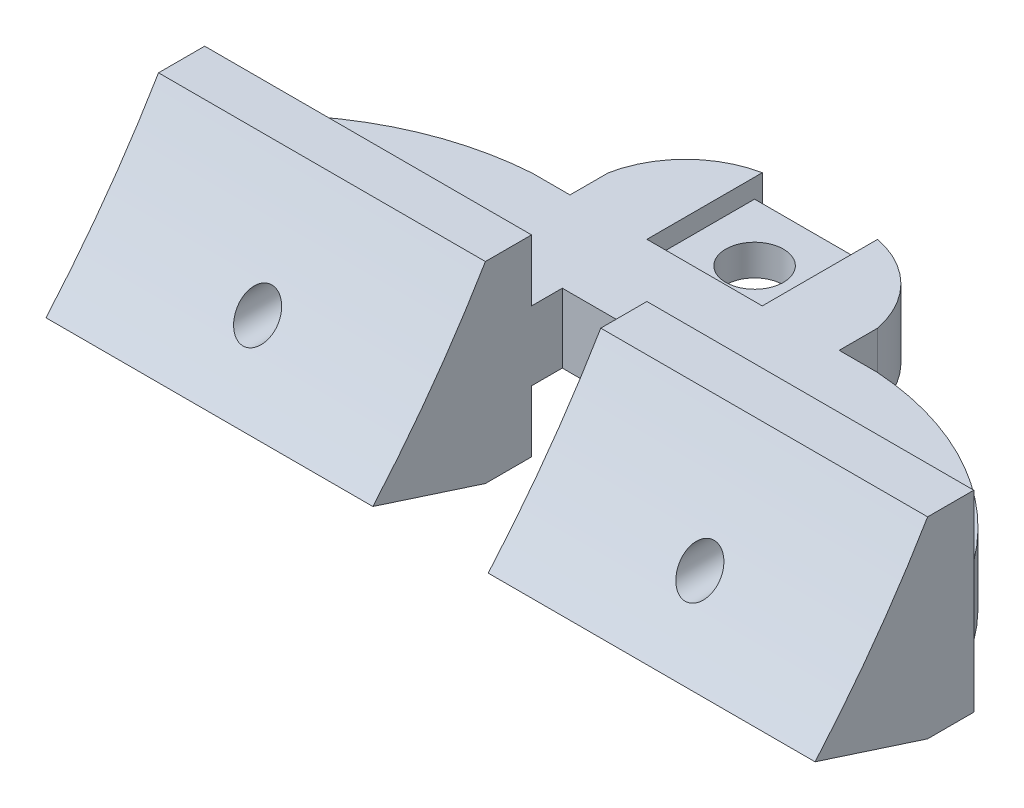
SolidWorks part; units mm, degrees
material "PMMA"
ref_plane "Plan de face" through (0, 0, 0) normal (0, 0, 1) x (1, 0, 0)
ref_plane "Plan de dessus" through (0, 0, 0) normal (0, 1, 0) x (1, 0, 0)
ref_plane "Plan de droite" through (0, 0, 0) normal (1, 0, 0) x (0, 0, -1)
sketch "Esquisse1" plane through (0, 0, 0) normal (0, 0, 1) x (1, 0, 0)
  line L1 (0, 0) -> (6, 0)
  line L2 (0, 0) -> (0, 1.61)
  line L3 (0, 1.61) -> (6, 1.61)
  line L4 (6, 0) -> (6, 1.61)
  dimension "D1" = 6
  dimension "D2" = 1.61
extrude "Boss.-Extru.1" add sketch "Esquisse1" against normal blind 6
sketch "Esquisse2" plane through (0, 0, 0) normal (0, 1, 0) x (1, 0, 0)
  line L0 (0, 6) -> (0, 0) construction
  line L1 (6, 0) -> (0, 0) construction
  circle A0 centre (3, 3) radius 1.5
  dimension "D3" = 3
  dimension "D1" = 3
  dimension "D2" = 3
extrude "Enlèv. mat.-Extru.3" cut sketch "Esquisse2" along normal through all contours A0
sketch "Esquisse5" plane through (0, 0, 0) normal (0, 0, 1) x (1, 0, 0)
  line L0 (0, 0) -> (6, 0) construction
  line L1 (3, 0.8) -> (-17, 0.8)
  line L2 (3, 0.8) -> (3, 5.8)
  line L3 (3, 5.8) -> (-17, 5.8)
  line L4 (-17, 0.8) -> (-17, 5.8)
  line L5 (3, 0.8) -> (-17, 0.8)
  line L6 (3, 0.8) -> (3, -4.2)
  line L7 (3, -4.2) -> (-17, -4.2)
  line L8 (-17, 0.8) -> (-17, -4.2)
  line L9 (3, 0.8) -> (23, 0.8)
  line L10 (3, 0.8) -> (3, 5.8)
  line L11 (3, 5.8) -> (23, 5.8)
  line L12 (23, 0.8) -> (23, 5.8)
  line L13 (3, 0.8) -> (23, 0.8)
  line L14 (3, 0.8) -> (3, -4.2)
  line L15 (3, -4.2) -> (23, -4.2)
  line L16 (23, 0.8) -> (23, -4.2)
  dimension "D1" = 0.8
  dimension "D2" = 5
  dimension "D3" = 5
  dimension "D4" = 20
  dimension "D5" = 20
extrude "Boss.-Extru.2" add sketch "Esquisse5" along normal blind 8 separate body contours L2 L1 L4 L3 | L10 L9 L12 L11 | L14 L13 L16 L15 | L6 L5 L8 L7
sketch "Esquisse6" plane through (0, 0, 0) normal (0, 0, -1) x (-1, 0, 0)
  line L1 (-23, 5.8) -> (17, 5.8)
  line L2 (-23, 5.8) -> (-23, -4.2)
  line L3 (-23, -4.2) -> (17, -4.2)
  line L4 (17, 5.8) -> (17, -4.2)
extrude "Boss.-Extru.3" add sketch "Esquisse6" along normal blind 0.4
sketch "Esquisse7" plane through (0, 0, -0.4) normal (0, 0, -1) x (-1, 0, 0)
  line L1 (0, 1.61) -> (4, 1.61)
  line L2 (0, 1.61) -> (0, 0.01)
  line L3 (0, 0.01) -> (4, 0.01)
  line L4 (4, 1.61) -> (4, 0.01)
  line L5 (0, 1.61) -> (4, 1.61)
  line L6 (0, 1.61) -> (0, 2.61)
  line L7 (0, 2.61) -> (4, 2.61)
  line L8 (4, 1.61) -> (4, 2.61)
  line L9 (0, 0.01) -> (4, 0.01)
  line L10 (0, 0.01) -> (0, -0.99)
  line L11 (0, -0.99) -> (4, -0.99)
  line L12 (4, 0.01) -> (4, -0.99)
  line L13 (-6, 0) -> (-10, 0)
  line L14 (-6, 0) -> (-6, 1.6)
  line L15 (-6, 1.6) -> (-10, 1.6)
  line L16 (-10, 0) -> (-10, 1.6)
  line L17 (-10, 1.6) -> (-6, 1.6)
  line L18 (-10, 1.6) -> (-10, 2.6)
  line L19 (-10, 2.6) -> (-6, 2.6)
  line L20 (-6, 1.6) -> (-6, 2.6)
  line L21 (-10, 0) -> (-6, 0)
  line L22 (-10, 0) -> (-10, -1)
  line L23 (-10, -1) -> (-6, -1)
  line L24 (-6, 0) -> (-6, -1)
  line M16 (0, 1.61) -> (0, 0)
  line M18 (-6, 0) -> (-6, 1.61)
  dimension "D1" = 4
  dimension "D2" = 4
  dimension "D3" = 1
  dimension "D4" = 1
  dimension "D5" = 1
  dimension "D6" = 1
  dimension "D7" = 1.6
extrude "Boss.-Extru.4" add sketch "Esquisse7" along normal blind 6 contours L24 L13 L22 L23 | L15 L20 L19 L18 | L16 L13 L15 M18 | L1 L8 L7 L6 | L4 L1 L3 M16 | L12 L3 L10 L11 region at (-2, 2.11, -0.4) region at (-2, 0.81, -0.4) region at (-2, -0.49, -0.4) region at (8, -0.5, -0.4) region at (8, 0.8, -0.4) region at (8, 2.1, -0.4)
sketch "Esquisse8" plane through (0, -1, 0) normal (0, -1, 0) x (1, 0, 0)
  line L1 (10, -0.4) -> (6, -0.4)
  line L2 (10, -0.4) -> (10, -6.4)
  line L3 (10, -6.4) -> (6, -6.4)
  line L4 (6, -0.4) -> (6, -6.4)
  line L5 (0, -6.4) -> (-4, -6.4)
  line L6 (0, -6.4) -> (0, -0.4)
  line L7 (0, -0.4) -> (-4, -0.4)
  line L8 (-4, -6.4) -> (-4, -0.4)
  arc A0 (0, -6.4) -> (-4, -0.4) centre (1, -1.4) cw
  arc A1 (6, -6.4) -> (10, -0.4) centre (5, -1.4) ccw
  line M3 (6, -6.4) -> (10, -6.4)
  line M4 (10, -6.4) -> (10, -0.4)
extrude "Enlèv. mat.-Extru.4" cut sketch "Esquisse8" against normal blind 6 contours A1 M3 M4 | L5 A0 L8 region at (8.9616, -1, -5.3616) region at (-2.9616, -1, -5.3616)
sketch "Esquisse9" plane through (0, 0, 8) normal (0, 0, 1) x (1, 0, 0)
  line L0 (-17, -4.2) -> (23, -4.2) construction
  line L1 (-17, 5.8) -> (0, 5.8)
  line L2 (-17, 5.8) -> (-17, -4.2)
  line L3 (-17, -4.2) -> (0, -4.2)
  line L4 (0, 5.8) -> (0, -4.2)
  line L6 (0, 5.8) -> (6, 5.8)
  line L7 (0, 5.8) -> (0, -4.2)
  line L8 (0, -4.2) -> (6, -4.2)
  line L9 (6, 5.8) -> (6, -4.2)
  line M4 (-17, -4.2) -> (23, -4.2)
  line M6 (23, 5.8) -> (-17, 5.8)
  dimension "D1" = 17
  dimension "6" = 6
extrude "Enlèv. mat.-Extru.5" cut sketch "Esquisse9" against normal blind 4 contours L9 L4 M6 M4 region at (3, 0.8, 8)
sketch "Esquisse10" plane through (0, -4.2, 0) normal (0, -1, 0) x (1, 0, 0)
  line L0 (-17, -0.4) -> (-17, 8) construction
  line L1 (-17, 5.6) -> (0, 5.6)
  line L2 (-17, 5.6) -> (-17, -0.4)
  line L3 (-17, -0.4) -> (0, -0.4)
  line L4 (0, 5.6) -> (0, -0.4)
  line L5 (23, -0.4) -> (-17, -0.4) construction
  line L6 (0, -0.4) -> (6, -0.4) construction
  line L7 (23, -0.4) -> (23, 8) construction
  line L8 (6, -0.4) -> (23, -0.4)
  line L9 (6, -0.4) -> (6, 5.6)
  line L10 (6, 5.6) -> (23, 5.6)
  line L11 (23, -0.4) -> (23, 5.6)
  line L13 (0, -0.4) -> (6, -0.4)
  line L14 (0, -0.4) -> (0, 4)
  line L15 (0, 4) -> (6, 4)
  line L16 (6, -0.4) -> (6, 4)
  line M5 (6, 8) -> (6, 4)
  line M6 (6, 4) -> (0, 4)
  line M7 (0, 4) -> (0, 8)
  line M9 (-17, 8) -> (-17, -0.4)
  line M10 (-17, -0.4) -> (23, -0.4)
  line M11 (23, -0.4) -> (23, 8)
  dimension "D1" = 6
  dimension "D2" = 6
extrude "Enlèv. mat.-Extru.6" cut sketch "Esquisse10" against normal blind 3.2 contours L4 L1 M7 M9 M10 | L9 L4 M10 M6 | L10 L9 M5 M10 M11 region at (-8.5, -4.2, 2.6) region at (3, -4.2, 1.8) region at (14.5, -4.2, 2.6)
sketch "Esquisse11" plane through (0, 5.8, 0) normal (0, 1, 0) x (1, 0, 0)
  line L0 (0, -4) -> (0, -8) construction
  line L1 (-17, 0.4) -> (0, 0.4)
  line L2 (-17, 0.4) -> (-17, -5.6)
  line L3 (-17, -5.6) -> (0, -5.6)
  line L4 (0, 0.4) -> (0, -5.6)
  line L5 (23, 0.4) -> (23, -8) construction
  line L6 (6, 0.4) -> (23, 0.4)
  line L7 (6, 0.4) -> (6, -5.6)
  line L8 (6, -5.6) -> (23, -5.6)
  line L9 (23, 0.4) -> (23, -5.6)
  line L11 (0, 0.4) -> (6, 0.4)
  line L12 (0, 0.4) -> (0, -4)
  line L13 (0, -4) -> (6, -4)
  line L14 (6, 0.4) -> (6, -4)
  line M7 (6, -4) -> (6, -8)
  line M9 (23, -8) -> (23, 0.4)
  line M10 (23, 0.4) -> (-17, 0.4)
  line M11 (-17, 0.4) -> (-17, -8)
  line M13 (0, -8) -> (0, -4)
  line M14 (0, -4) -> (6, -4)
  dimension "D1" = 6
  dimension "D2" = 6
extrude "Enlèv. mat.-Extru.7" cut sketch "Esquisse11" against normal blind 3.2 contours L4 L3 M10 M11 M13 | L7 L4 M10 M14 | L8 L7 M7 M9 M10 region at (-8.5, 5.8, 2.6) region at (3, 5.8, 1.8) region at (14.5, 5.8, 2.6)
sketch "Esquisse12" plane through (0, -0.99, 0) normal (0, -1, 0) x (1, 0, 0)
  line L0 (0, -6.4) -> (0, -2.4)
  line L1 (0, -0.4) -> (-4, -0.4)
  line L2 (0, -0.4) -> (0, -2.4)
  line L3 (0, -2.4) -> (-4, -2.4)
  line L4 (-4, -0.4) -> (-4, -2.4)
  arc A0 (0, -6.4) -> (-4, -0.4) centre (1, -1.4) cw
  line M1 (-4, -0.4) -> (-4, -2.4)
  arc M2 (-4, -2.4) -> (0, -6.4) centre (1, -1.4) ccw
  line M3 (0, -6.4) -> (0, -0.4)
  line M4 (0, -0.4) -> (-4, -0.4)
extrude "Boss.-Extru.5" add sketch "Esquisse12" along normal blind 0.01 and the other way blind 3.61 contours L3 M3 M2 | L3 M3 M4 M1 region at (-1.5986, -0.99, -3.9986) region at (-2, -0.99, -1.4)
sketch "Esquisse13" plane through (0, 0, -0.4) normal (0, 0, 1) x (1, 0, 0)
  line L0 (0, 2.62) -> (-4, 2.62) construction
  line L1 (0, 2.6) -> (-3.9968, 2.6)
  line L2 (0, 2.6) -> (0, 2.62)
  line L3 (0, 2.62) -> (-3.9968, 2.62)
  line L4 (-3.9968, 2.6) -> (-3.9968, 2.62)
  line L6 (-3.9968, 2.6) -> (-4, 2.6)
  line L7 (-3.9968, 2.6) -> (-3.9968, 2.62)
  line L8 (-3.9968, 2.62) -> (-4, 2.62)
  line L9 (-4, 2.6) -> (-4, 2.62)
  line M1 (0, 2.6) -> (0, 2.62)
  line M2 (0, 2.62) -> (-4, 2.62)
  line M3 (-4, 2.62) -> (-4, 2.6)
  line M4 (-4, 2.6) -> (0, 2.6)
extrude "Enlèv. mat.-Extru.8" cut sketch "Esquisse13" against normal through all contours L4 M4 M1 M2 | L4 M4 M2 M3 region at (-1.9984, 2.61, -0.4) region at (-3.9984, 2.61, -0.4)
sketch "Esquisse14" plane through (0, -1, 0) normal (0, -1, 0) x (1, 0, 0)
  line L1 (-17, 5.6) -> (-4, 5.6)
  line L2 (-17, 5.6) -> (-17, -0.4)
  line L3 (-17, -0.4) -> (-4, -0.4)
  line L4 (-4, 5.6) -> (-4, -0.4)
  line L5 (10, -0.4) -> (23, -0.4)
  line L6 (10, -0.4) -> (10, 5.6)
  line L7 (10, 5.6) -> (23, 5.6)
  line L8 (23, -0.4) -> (23, 5.6)
  arc A0 (-17, 5.6) -> (-4, -0.4) centre (-4.9762, 14.5682) ccw
  arc A1 (10, -0.4) -> (23, 5.6) centre (10.9762, 14.5682) ccw
  line M4 (23, -0.4) -> (23, 5.6)
  line M10 (-17, 5.6) -> (-17, -0.4)
  line M11 (-17, -0.4) -> (-4, -0.4)
extrude "Enlèv. mat.-Extru.9" cut sketch "Esquisse14" against normal through all contours A0 M10 M11 | A1 L5 M4 region at (-14.1757, -1, 1.3209) region at (20.1757, -1, 1.3209)
sketch "Esquisse15" plane through (23, 0, 0) normal (1, 0, 0) x (0, 0, -1)
  line L0 (-13.8523, -2.3087) -> (-8, -4.2)
  line L7 (-5.6, -1) -> (-5.6, 2.6)
  line L8 (-5.6, 2.6) -> (-5.6, 5.8)
  line L9 (-5.6, 5.8) -> (-8, 5.8)
  line L10 (-8, 5.8) -> (-8, -4.2)
  line L11 (-8, -4.2) -> (-5.6, -4.2)
  line L12 (-5.6, -4.2) -> (-5.6, -1)
  line L16 (-8, 5.8) -> (-8, -4.2)
  arc A0 (-8, 5.8) -> (-13.8523, -2.3087) centre (-55.3392, 33.8) cw
  dimension "D1" = 28
  dimension "D4" = 0
  dimension "D3" = 10
  dimension "D2" = 55
extrude "Boss.-Extru.6" add sketch "Esquisse15" against normal blind 17
pattern_linear "Répétition linéaire1" count 2 spacing 23 along (-1, 0, 0) of "Boss.-Extru.6"
sketch "Esquisse17" plane through (0, 0, 5.6) normal (0, 0, -1) x (-1, 0, 0)
  line L0 (-6, -4.2) -> (-23, -4.2) construction
  line L1 (17, -4.2) -> (0, -4.2) construction
  line L2 (-23, 2.6) -> (-23, -1) construction
  line L3 (17, 2.6) -> (17, -1) construction
  circle A0 centre (8.5, 0.8) radius 1
  circle A1 centre (-14.5, 0.8) radius 1
  dimension "D1" = 2
  dimension "D2" = 2
  dimension "D3" = 5
  dimension "D4" = 5
  dimension "D5" = 8.5
  dimension "D6" = 8.5
extrude "Enlèv. mat.-Extru.10" cut sketch "Esquisse17" against normal through all both and the other way through all
